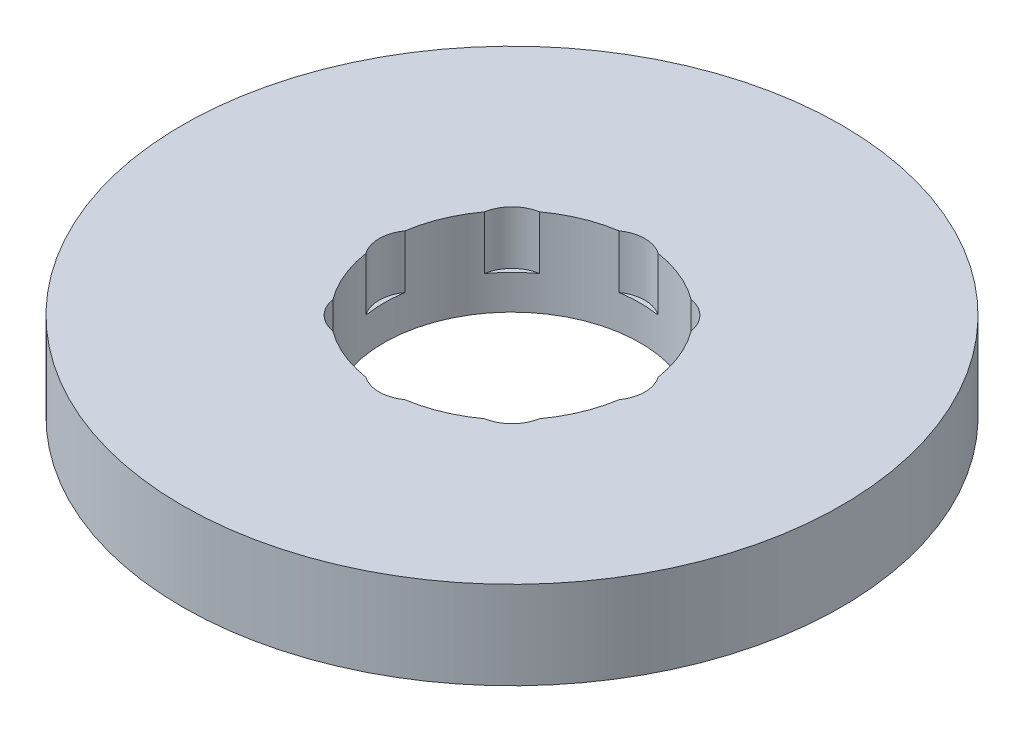
SolidWorks part; units mm, degrees
ref_plane "Front Plane" through (0, 0, 0) normal (0, 0, 1) x (1, 0, 0)
ref_plane "Top Plane" through (0, 0, 0) normal (0, 1, 0) x (1, 0, 0)
ref_plane "Right Plane" through (0, 0, 0) normal (1, 0, 0) x (0, 0, -1)
sketch "Sketch1" plane through (0, 0, 0) normal (0, 1, 0) x (1, 0, 0)
  circle A0 centre (0, 0) radius 45
  dimension "FLANGE_OD" = 90
extrude "Boss-Extrude1" add sketch "Sketch1" along normal blind 12
sketch "Sketch2" plane through (0, 0, 0) normal (0, 1, 0) x (1, 0, 0)
  circle A0 centre (0, 0) radius 17.5
  dimension "BORE_D" = 35
extrude "Cut-Extrude1" cut sketch "Sketch2" along normal through all
sketch "Sketch3" plane through (0, 12, 0) normal (0, 1, 0) x (1, 0, 0)
  circle A0 centre (0, 0) radius 13.5594 construction
  circle A1 centre (-13.5594, 0) radius 4.5848
  dimension "BOLT_D" = 9.1695
  dimension "BOLT_PCD" = 27.1187
extrude "Cut-Extrude2" cut sketch "Sketch3" against normal blind 7.2912
pattern_circular "CirPattern1" count 8 over 360 about axis through (0, 0, 0) along (0, 1, 0) of "Cut-Extrude2"
